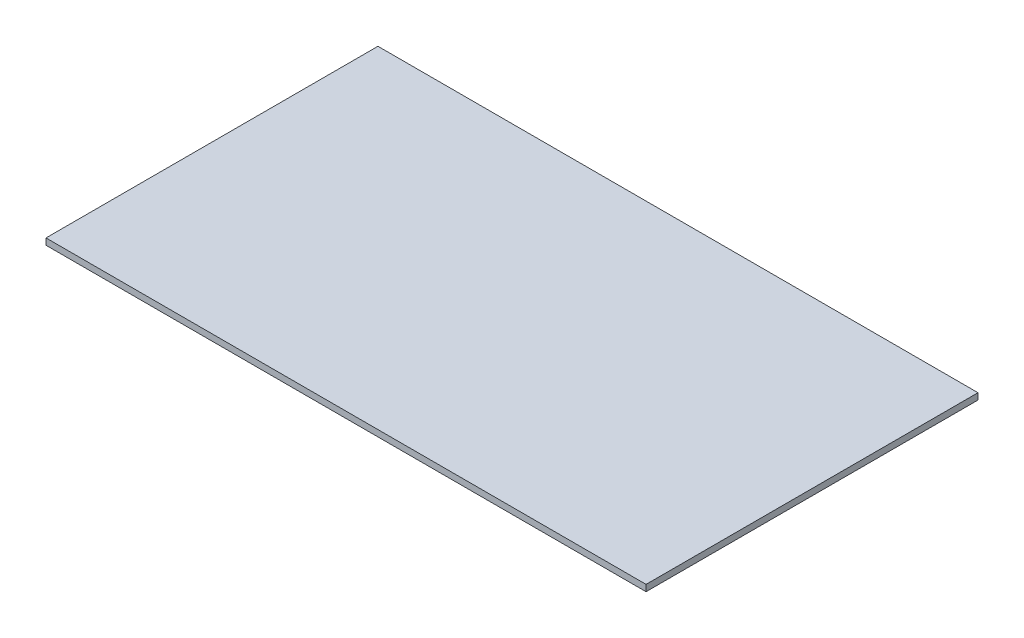
SolidWorks part; units mm, degrees
ref_plane "正面" through (0, 0, 0) normal (0, 0, 1) x (1, 0, 0)
ref_plane "平面" through (0, 0, 0) normal (0, 1, 0) x (1, 0, 0)
ref_plane "右側面" through (0, 0, 0) normal (1, 0, 0) x (0, 0, -1)
sketch "ｽｹｯﾁ1" plane through (0, 0, 0) normal (0, 1, 0) x (1, 0, 0)
  line L1 (-235, 130) -> (235, 130)
  line L2 (-235, 130) -> (-235, -130)
  line L3 (-235, -130) -> (235, -130)
  line L4 (235, 130) -> (235, -130)
  line L5 (-235, 130) -> (235, -130) construction
  line L6 (-235, -130) -> (235, 130) construction
  point P0 (0, 0)
  dimension "D1" = 260
  dimension "D2" = 470
extrude "ﾎﾞｽ - 押し出し1" add sketch "ｽｹｯﾁ1" along normal blind 5
